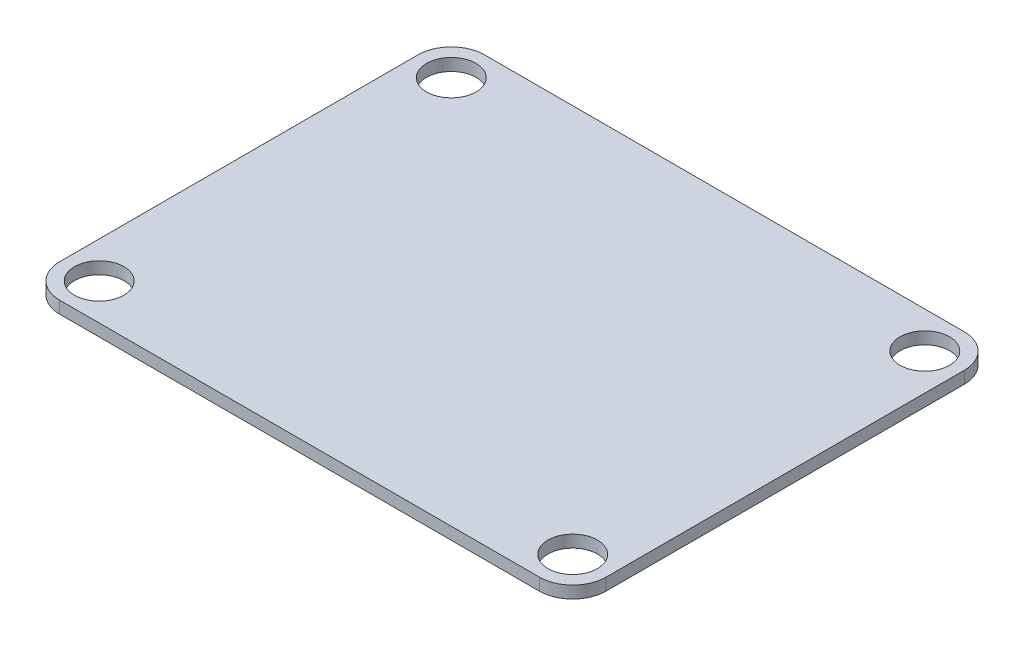
SolidWorks part; units mm, degrees
ref_plane "Front Plane" through (0, 0, 0) normal (0, 0, 1) x (1, 0, 0)
ref_plane "Top Plane" through (0, 0, 0) normal (0, 1, 0) x (1, 0, 0)
ref_plane "Right Plane" through (0, 0, 0) normal (1, 0, 0) x (0, 0, -1)
sketch "Sketch1" plane through (0, 0, 0) normal (0, 1, 0) x (1, 0, 0)
  line L1 (-114.3, 88.9) -> (114.3, 88.9)
  line L2 (-114.3, 88.9) -> (-114.3, -88.9)
  line L3 (-114.3, -88.9) -> (114.3, -88.9)
  line L4 (114.3, 88.9) -> (114.3, -88.9)
  line L5 (-114.3, 88.9) -> (114.3, -88.9) construction
  line L6 (-114.3, -88.9) -> (114.3, 88.9) construction
  point P0 (0, 0)
  dimension "D1" = 177.8
  dimension "10" = 228.6
extrude "Boss-Extrude1" add sketch "Sketch1" along normal blind 5.08
sketch "Sketch2" plane through (0, 5.08, 0) normal (0, 1, 0) x (1, 0, 0)
  line L0 (-99.06, 73.66) -> (-99.06, 88.9) construction
  line L1 (114.3, 88.9) -> (-114.3, 88.9) construction
  line L2 (-99.06, 73.66) -> (-114.3, 73.66) construction
  line L3 (-114.3, 88.9) -> (-114.3, -88.9) construction
  line L4 (-99.06, -73.66) -> (-114.3, -73.66) construction
  line L5 (-99.06, -73.66) -> (-99.06, -88.9) construction
  line L6 (-114.3, -88.9) -> (114.3, -88.9) construction
  line L7 (99.06, 73.66) -> (99.06, 88.9) construction
  line L8 (99.06, 73.66) -> (114.3, 73.66) construction
  line L9 (114.3, -88.9) -> (114.3, 88.9) construction
  line L10 (99.06, -73.66) -> (99.06, -88.9) construction
  line L11 (99.06, -73.66) -> (114.3, -73.66) construction
  circle A0 centre (-99.06, 73.66) radius 10.3505
  circle A1 centre (99.06, 73.66) radius 10.3505
  circle A2 centre (99.06, -73.66) radius 10.3505
  circle A3 centre (-99.06, -73.66) radius 10.3505
  dimension "D1" = 20.701
  dimension "D2" = 15.24
extrude "Cut-Extrude1" cut sketch "Sketch2" against normal through all
fillet "Fillet3" radius 13.97 4 edges at (114.3, 2.54, -88.9) (114.3, 2.54, 88.9) (-114.3, 2.54, -88.9) (-114.3, 2.54, 88.9)
sketch "Sketch3" plane through (0, 5.08, 0) normal (0, 1, 0) x (1, 0, 0)
  line L0 (-114.3, 0) -> (114.3, 0) construction
  line L1 (-114.3, 74.93) -> (-114.3, -74.93) construction
  line L2 (114.3, -74.93) -> (114.3, 74.93) construction
  line L3 (0, 88.9) -> (0, -88.9) construction
  line L4 (100.33, 88.9) -> (-100.33, 88.9) construction
  line L5 (-100.33, -88.9) -> (100.33, -88.9) construction
  point P12 (0, 0)
sketch "Sketch4" plane through (0, 5.08, 0) normal (0, 1, 0) x (1, 0, 0)
  line L0 (-106.3789, 80.9789) -> (-99.06, 73.66) construction
  line L5 (-106.3789, 80.9789) -> (-110.2083, 84.8083) construction
  line L6 (-114.3, 0) -> (114.3, 0) construction
  line L7 (0, 88.9) -> (0, -88.9) construction
  line L8 (-114.3, 0) -> (114.3, 0) construction
  line L9 (0, 88.9) -> (0, -88.9) construction
  arc A0 (-100.33, 88.9) -> (-114.3, 74.93) centre (-100.33, 74.93) ccw construction
  circle A1 centre (-99.06, 73.66) radius 10.3505 construction
  circle A2 centre (-108.2936, 82.8936) radius 2
  circle A3 centre (108.2936, 82.8936) radius 2
  circle A4 centre (108.2936, -82.8936) radius 2
  circle A5 centre (-108.2936, -82.8936) radius 2
  point P6 (-99.06, 73.66)
  dimension "D2" = 4
sketch "Sketch5" plane through (0, 5.08, 0) normal (0, 1, 0) x (1, 0, 0)
  line L0 (-99.06, 73.66) -> (-99.06, 88.9) construction
  line L1 (100.33, 88.9) -> (-100.33, 88.9) construction
  line L2 (-99.06, 73.66) -> (-114.2422, 73.66) construction
  circle A0 centre (-100.33, 74.93) radius 13.97
  arc A1 (-100.33, 88.9) -> (-114.3, 74.93) centre (-100.33, 74.93) ccw construction
  circle A2 centre (-99.06, 73.66) radius 7.62
  point P8 (-99.06, 73.66)
  dimension "D1" = 15.24
